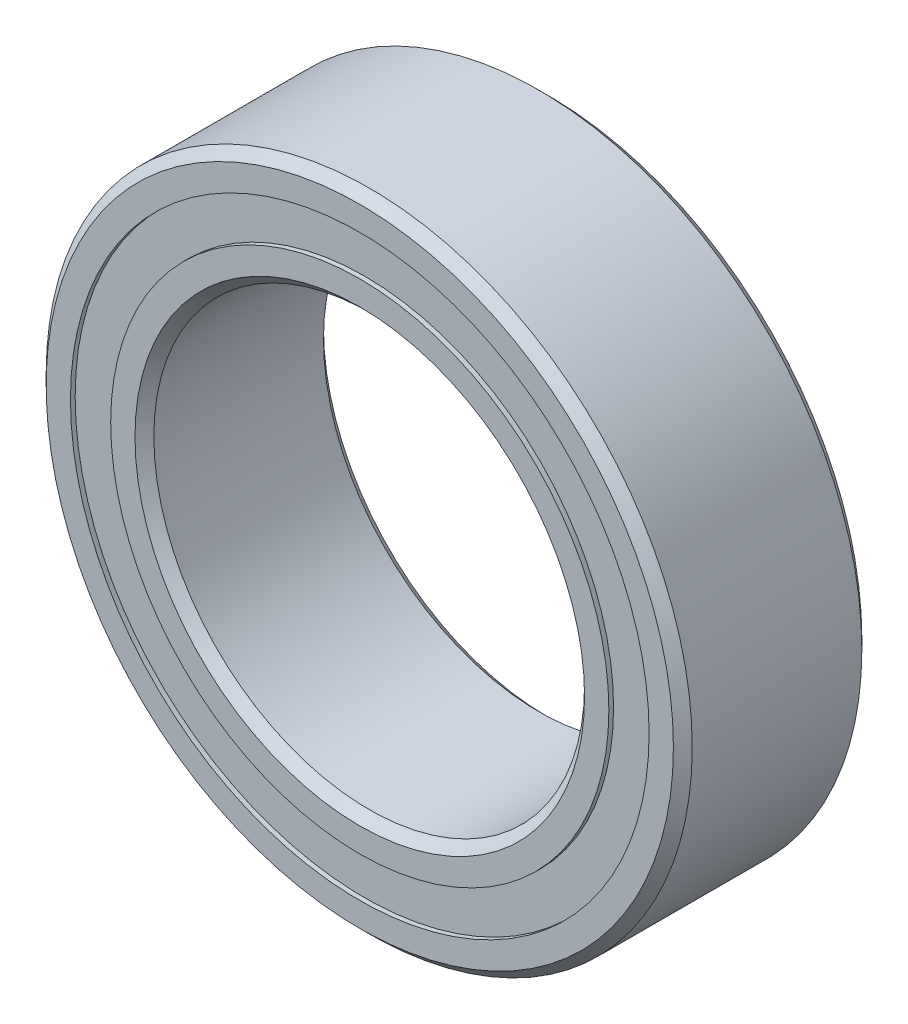
SolidWorks part; units mm, degrees
ref_plane "Front Plane" through (0, 0, 0) normal (0, 0, 1) x (1, 0, 0)
ref_plane "Top Plane" through (0, 0, 0) normal (0, 1, 0) x (1, 0, 0)
ref_plane "Right Plane" through (0, 0, 0) normal (1, 0, 0) x (0, 0, -1)
sketch "Sketch1" plane through (0, 0, 0) normal (1, 0, 0) x (0, 0, -1)
  line L0 (-1.75, 0) -> (1.75, 0) construction
  line L1 (0, 6) -> (0, -6) construction
  line L2 (1.575, 6) -> (-1.575, 6)
  line L3 (-1.575, 6) -> (-1.75, 5.825)
  line L4 (-1.75, 5.825) -> (-1.75, 5.3736)
  line L5 (-1.75, 5.3736) -> (-0.7778, 5.3736)
  line L6 (1.75, 5.3736) -> (0.7778, 5.3736)
  line L7 (1.75, 5.825) -> (1.75, 5.3736)
  line L8 (1.575, 6) -> (1.75, 5.825)
  line L9 (0, 6) -> (0, 5) construction
  line L10 (0, 5) -> (0, 4) construction
  arc A0 (-0.7778, 5.3736) -> (0.7778, 5.3736) centre (0, 5) cw
  point P14 (0, 4)
  dimension "D3" = 1.5556
  dimension "D1" = 45
  dimension "Width" = 3.5
  dimension "OD" = 12
  dimension "D2" = 0.175
  dimension "Shaft Dia" = 8
  dimension "D4" = 0.3736
revolve "Revolve1" add sketch "Sketch1" angle 360 about L0
sketch "Sketch3" plane through (0, 0, 0) normal (1, 0, 0) x (0, 0, -1)
  line L0 (-1.75, 4.6264) -> (-0.7778, 4.6264)
  line L1 (0, 6) -> (0, -6) construction
  line L2 (-1.75, 5.825) -> (-1.75, 5.3736) construction
  line L3 (-1.75, 4.6264) -> (-1.75, 4.175)
  line L4 (-1.575, 6) -> (-1.75, 5.825) construction
  line L5 (-1.75, 4.175) -> (-1.575, 4)
  line L6 (-1.575, 4) -> (1.575, 4)
  line L7 (1.575, 6) -> (1.575, -6) construction
  line L8 (1.575, 4) -> (1.75, 4.175)
  line L9 (1.75, -5.825) -> (1.75, 5.825) construction
  line L10 (1.75, 4.175) -> (1.75, 4.6264)
  line L11 (1.75, 4.6264) -> (0.7778, 4.6264)
  line L13 (1.575, 6) -> (1.75, 5.825) construction
  arc A0 (0.7778, 5.3736) -> (-0.7778, 5.3736) centre (0, 5) ccw construction
  arc A1 (0.7778, 4.6264) -> (-0.7778, 4.6264) centre (0, 5) cw
revolve "Revolve3" add sketch "Sketch3" angle 360 about L0
sketch "Sketch4" plane through (0, 0, 0) normal (1, 0, 0) x (0, 0, -1)
  line L0 (-0.8629, 5) -> (0.8629, 5)
  arc A2 (-0.8629, 5) -> (0.8629, 5) centre (0, 5) cw
  arc A3 (0.7778, 5.3736) -> (-0.7778, 5.3736) centre (0, 5) ccw construction
revolve "Revolve4" add sketch "Sketch4" angle 360 about L0
ref_axis "Axis1" through (0, 0, -1.75) along (0, 0, 1)
pattern_circular "CirPattern1" count 12 every 30 about axis through (0, 0, -1.75) along (0, 0, 1) of bodies 104
sketch "Sketch5" plane through (0, 0, 0) normal (1, 0, 0) x (0, 0, -1)
  line L0 (-1.75, 5.3736) -> (-0.7778, 5.3736) construction
  line L1 (-1.6625, 5.3736) -> (-0.8629, 5.3736)
  line L2 (-1.6625, 5.3736) -> (-1.6625, 4.6264)
  line L3 (-1.6625, 4.6264) -> (-0.8629, 4.6264)
  line L4 (-0.8629, 5.3736) -> (-0.8629, 4.6264)
  line L5 (-1.75, 4.6264) -> (-0.7778, 4.6264) construction
  line L6 (1.75, 5.3736) -> (0.7778, 5.3736) construction
  line L7 (1.6625, 5.3736) -> (0.8629, 5.3736)
  line L8 (1.6625, 5.3736) -> (1.6625, 4.6264)
  line L9 (1.6625, 4.6264) -> (0.8629, 4.6264)
  line L10 (0.8629, 5.3736) -> (0.8629, 4.6264)
  line L11 (1.75, 4.6264) -> (0.7778, 4.6264) construction
  line L12 (-1.575, 6) -> (-1.75, 5.825) construction
  point P18 (-1.6625, 5.9125)
revolve "Revolve5" add sketch "Sketch5" angle 360 about L0
sketch "Sketch6" plane through (0, 0, 0) normal (1, 0, 0) x (0, 0, -1)
  line L0 (1.75, 0) -> (-1.75, 0) construction
  line L1 (1.75, 5.3736) -> (0.9626, 5.3736)
  line L2 (1.75, 5.3736) -> (1.75, 6.9469)
  line L3 (1.75, 6.9469) -> (0.9626, 6.9469)
  line L4 (0.9626, 5.3736) -> (0.9626, 6.9469)
  dimension "Th" = 0.7874
  dimension "Flange OD" = 13.8938
revolve "Revolve6" [suppressed] add sketch "Sketch6" angle 360 about L0
equation "\"D2@Sketch1\" = \"Width@Sketch1\"*.05"
equation "\"D3@Sketch1\" = \"Width@Sketch1\"/2.25"
equation "\"D4@Sketch1\" = (((\"OD@Sketch1\"-\"Width@Sketch1\")/2)/3.25)/3.5"
equation "\"D2@CirPattern1\" = 360/\"Balls@CirPattern1\""
